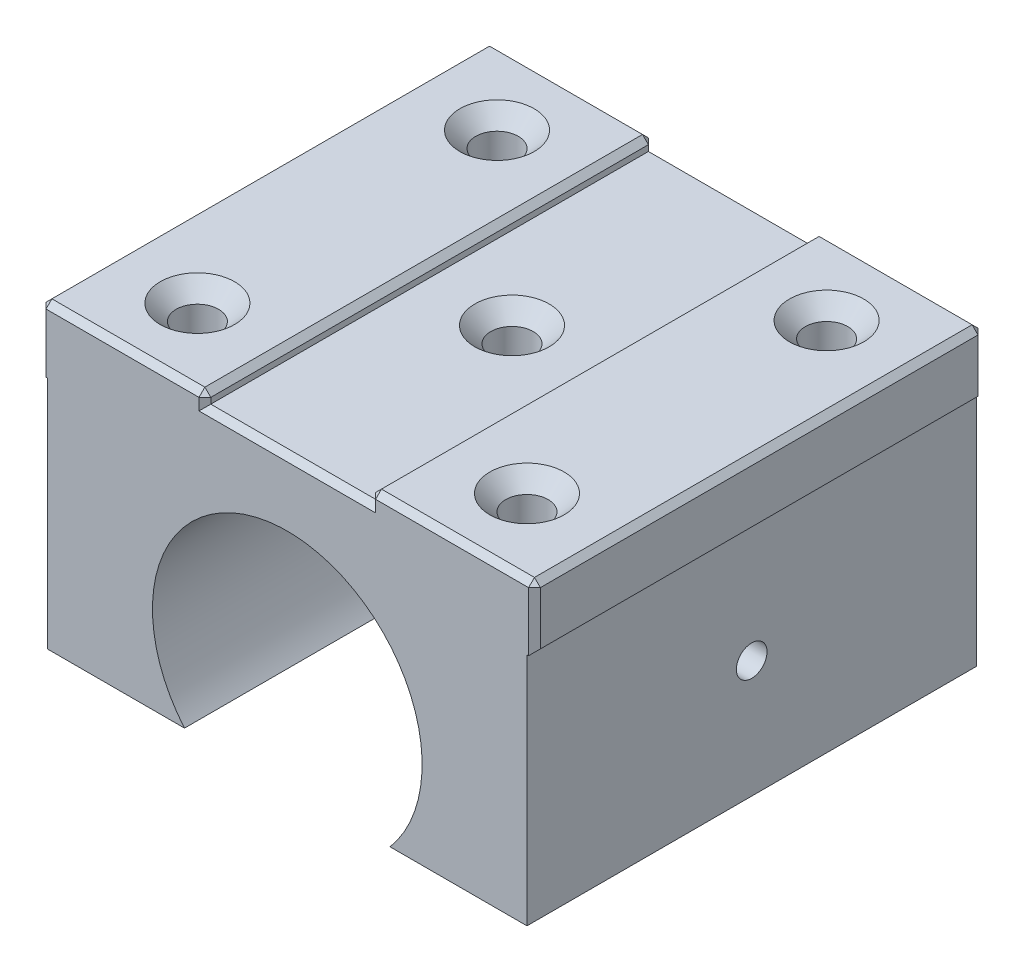
SolidWorks part; units mm, degrees
ref_plane "Front Plane" through (0, 0, 0) normal (0, 0, 1) x (1, 0, 0)
ref_plane "Top Plane" through (0, 0, 0) normal (0, 1, 0) x (1, 0, 0)
ref_plane "Right Plane" through (0, 0, 0) normal (1, 0, 0) x (0, 0, -1)
sketch "Sketch1" plane through (0, 0, 0) normal (0, 0, 1) x (1, 0, 0)
  line L0 (0, 0) -> (0, 11.43) construction
  line L1 (-20.32, -7.3995) -> (-8.7116, -7.3995)
  line L2 (-20.32, -7.3995) -> (-20.32, 12.5005)
  line L3 (-20.955, 18.0005) -> (20.955, 18.0005)
  line L4 (20.32, -7.3995) -> (20.32, 12.5005)
  line L5 (8.7116, -7.3995) -> (20.32, -7.3995)
  line L6 (20.32, 12.5005) -> (20.955, 12.5005)
  line L7 (-20.955, 18.0005) -> (20.955, 18.0005)
  line L8 (-20.955, 18.0005) -> (-20.955, 12.5005)
  line L9 (-20.955, 12.5005) -> (-20.32, 12.5005)
  line L10 (20.955, 18.0005) -> (20.955, 12.5005)
  line L11 (0, 18.0005) -> (0, 51.8376) construction
  line L13 (-20.955, 18.0005) -> (20.955, 18.0005)
  arc A0 (8.7116, -7.3995) -> (-8.7116, -7.3995) centre (0, 0) ccw
  dimension "D1" = 22.86
  dimension "D2" = 25.4
  dimension "D3" = 40.64
  dimension "D4" = 18.0005
  dimension "D5" = 5.5
  dimension "D6" = 41.91
extrude "Boss-Extrude1" add sketch "Sketch1" along normal blind 38.1 contours A0 L0 L3 L8 L9 L2 L1 | L0 A0 L5 L4 L6 L10 L7 region at (-19.8299, 2.5505, 0)
sketch "Sketch3" plane through (0, 18.0005, 0) normal (0, 1, 0) x (1, 0, 0)
  line L0 (0, 0) -> (0, -38.1) construction
  line L1 (-20.955, 0) -> (20.955, 0) construction
  line L2 (-20.955, -38.1) -> (20.955, -38.1) construction
  line L3 (-20.955, -19.05) -> (20.955, -19.05) construction
  line L4 (-20.955, -38.1) -> (-20.955, 0) construction
  line L5 (20.955, -38.1) -> (20.955, 0) construction
  line L6 (-13.97, -6.35) -> (-13.97, -31.75) construction
  line L7 (-6.985, 0) -> (-6.985, -38.1) construction
  line L8 (6.985, 0) -> (6.985, -38.1) construction
  line L11 (20.955, 0) -> (-20.955, 0)
  line L12 (-20.955, 0) -> (-20.955, -38.1)
  line L13 (-20.955, -38.1) -> (20.955, -38.1)
  line L14 (20.955, -38.1) -> (20.955, 0)
  line L15 (20.955, 0) -> (-20.955, 0) construction
  line L16 (-20.955, 0) -> (-20.955, -38.1) construction
  line L17 (-20.955, -38.1) -> (20.955, -38.1) construction
  line L18 (20.955, -38.1) -> (20.955, 0) construction
  circle A0 centre (-13.97, -6.35) radius 1
  circle A1 centre (13.97, -6.35) radius 1
  circle A2 centre (-13.97, -31.75) radius 1
  circle A3 centre (13.97, -31.75) radius 1
  circle A4 centre (0, -19.05) radius 1
  dimension "D3" = 2
  dimension "D4" = 2
  dimension "D1" = 27.94
  dimension "D2" = 25.4
  dimension "D5" = 0
sketch "Sketch4" plane through (0, 0, 38.1) normal (0, 0, 1) x (1, 0, 0)
  line L0 (-6.985, 18.0005) -> (-6.985, 17.0005)
  line L1 (-6.985, 17.0005) -> (6.985, 17.0005)
  line L2 (6.985, 17.0005) -> (6.985, 18.0005)
  dimension "D1" = 1
sketch "Sketch9" plane through (0, 18.0005, 0) normal (0, 1, 0) x (1, 0, 0)
  point P0 (-13.97, -6.35)
  point P3 (-13.97, -31.75)
  point P6 (13.97, -31.75)
  point P9 (13.97, -6.35)
hole_wizard "CSK for M3 Countersunk Flat Head Screw2" positions "Sketch9" profile "Sketch8" countersink size "M3" standard "ISO"
sketch "Sketch8" plane through (-13.97, 18.0005, 6.35) normal (1, 0, 0) x (0, 0, 1)
  line L0 (0, 0) -> (0, 11.0815)
  line L1 (0, 11.0815) -> (1.8, 10)
  line L2 (1.8, 10) -> (1.8, 1.35)
  line L3 (1.8, 1.35) -> (3.15, 0)
  line L5 (3.15, 0) -> (0, 0)
  line L6 (-1.8, 1.35) -> (-3.15, 0) construction
  line L10 (0, 11.0815) -> (-1.8, 10) construction
  line L11 (0, -6.35) -> (0, 107.95) construction
  dimension "Hole Dia." = 3.6
  dimension "Hole Depth" = 10
  dimension "Near C'Sink Dia." = 6.3
  dimension "Near C'Sink Angle" = 90
  dimension "Drill Angle" = 118
extrude "Cut-Extrude1" cut sketch "Sketch4" against normal through all and the other way through all
sketch "Sketch11" plane through (0, 17.0005, 0) normal (0, 1, 0) x (1, 0, 0)
  circle A0 centre (0, -19.05) radius 1 construction
  circle A1 centre (0, -19.05) radius 1
  point P2 (0, -19.05)
hole_wizard "CSK for M3 Countersunk Flat Head Screw3" positions "Sketch11" profile "Sketch12" countersink size "M3" standard "ISO"
sketch "Sketch12" plane through (0, 17.0005, 19.05) normal (1, 0, 0) x (0, 0, 1)
  line L0 (0, 0) -> (0, 11.0815)
  line L1 (0, 11.0815) -> (1.8, 10)
  line L2 (1.8, 10) -> (1.8, 1.35)
  line L3 (1.8, 1.35) -> (3.15, 0)
  line L5 (3.15, 0) -> (0, 0)
  line L6 (-1.8, 1.35) -> (-3.15, 0) construction
  line L10 (0, 11.0815) -> (-1.8, 10) construction
  line L11 (0, -6.35) -> (0, 107.95) construction
  dimension "Hole Dia." = 3.6
  dimension "Hole Depth" = 10
  dimension "Near C'Sink Dia." = 6.3
  dimension "Near C'Sink Angle" = 90
  dimension "Drill Angle" = 118
chamfer "Chamfer1" distance 0.5 angle 45 20 edges at (20.955, 12.5005, 19.05) (13.97, 18.0005, 0) (20.955, 15.2505, 0) (6.985, 17.5005, 0) (6.985, 17.5005, 38.1) (20.955, 18.0005, 19.05) (13.97, 18.0005, 38.1) (6.985, 18.0005, 19.05) (-6.985, 17.5005, 0) (-6.985, 17.5005, 38.1) (-13.97, 18.0005, 0) (-6.985, 18.0005, 19.05) (-13.97, 18.0005, 38.1) (-20.955, 18.0005, 19.05) (-20.955, 12.5005, 19.05) (0, 17.0005, 0) (0, 17.0005, 38.1) (-20.955, 15.2505, 0) (20.955, 15.2505, 38.1) (-20.955, 15.2505, 38.1)
sketch "Sketch13" plane through (-20.32, 0, 0) normal (-1, 0, 0) x (0, 0, 1)
  line L0 (0, 12.5005) -> (38.1, -7.3995) construction
  line L1 (0, -7.3995) -> (38.1, 12.5005) construction
  point P10 (19.05, 2.5505)
hole_wizard "CSK for M2 Countersunk Flat Head Screw2" positions "Sketch13" profile "Sketch14" countersink size "M2" standard "ISO" end condition through all
sketch "Sketch14" plane through (-20.32, 2.5505, 19.05) normal (0, 1, 0) x (0, 0, 1)
  line L0 (0, 0) -> (0, 41.275)
  line L1 (0, 41.275) -> (1.3, 41.275)
  line L2 (1.3, 41.275) -> (1.3, 0.9)
  line L3 (1.3, 0.9) -> (2.2, 0)
  line L5 (2.2, 0) -> (0, 0)
  line L6 (-1.3, 0.9) -> (-2.2, 0) construction
  line L11 (0, -6.35) -> (0, 107.95) construction
  dimension "Thru Hole Dia." = 2.6
  dimension "Thru Hole Depth" = 41.275
  dimension "Near C'Sink Dia." = 4.4
  dimension "Near C'Sink Angle" = 90
ref_plane "Plane1" through (0, 0, 33.1) normal (0, 0, 1) x (1, 0, 0)
ref_plane "Plane2" through (0, 0, 19.05) normal (0, 0, 1) x (1, 0, 0)
ref_plane "Plane3" through (0, 0, 5) normal (0, 0, -1) x (-1, 0, 0)
sketch "Sketch16" plane through (0, 0, 33.1) normal (0, 0, 1) x (1, 0, 0)
  line L0 (-8.0822, 8.0822) -> (0, 0) construction
  line L1 (0, 0) -> (8.0822, 8.0822) construction
  line L2 (0, 0) -> (0, 11.43) construction
  line L3 (-7.3751, 7.3751) -> (-8.7893, 8.7893)
  arc A0 (8.7116, -7.3995) -> (-8.7116, -7.3995) centre (0, 0) ccw construction
  arc A1 (-7.3751, 7.3751) -> (-8.7893, 8.7893) centre (-8.0822, 8.0822) ccw
  dimension "D2" = 2
  dimension "D1" = 90
revolve "Revolve4" add sketch "Sketch16" angle 360 about L0
mirror "Mirror1" about plane through (0, 0, 0) normal (1, 0, 0) of "Revolve4"
pattern_linear "LPattern1" count 10 spacing 3.1222 along (0, 0, -1) of "Mirror1"
